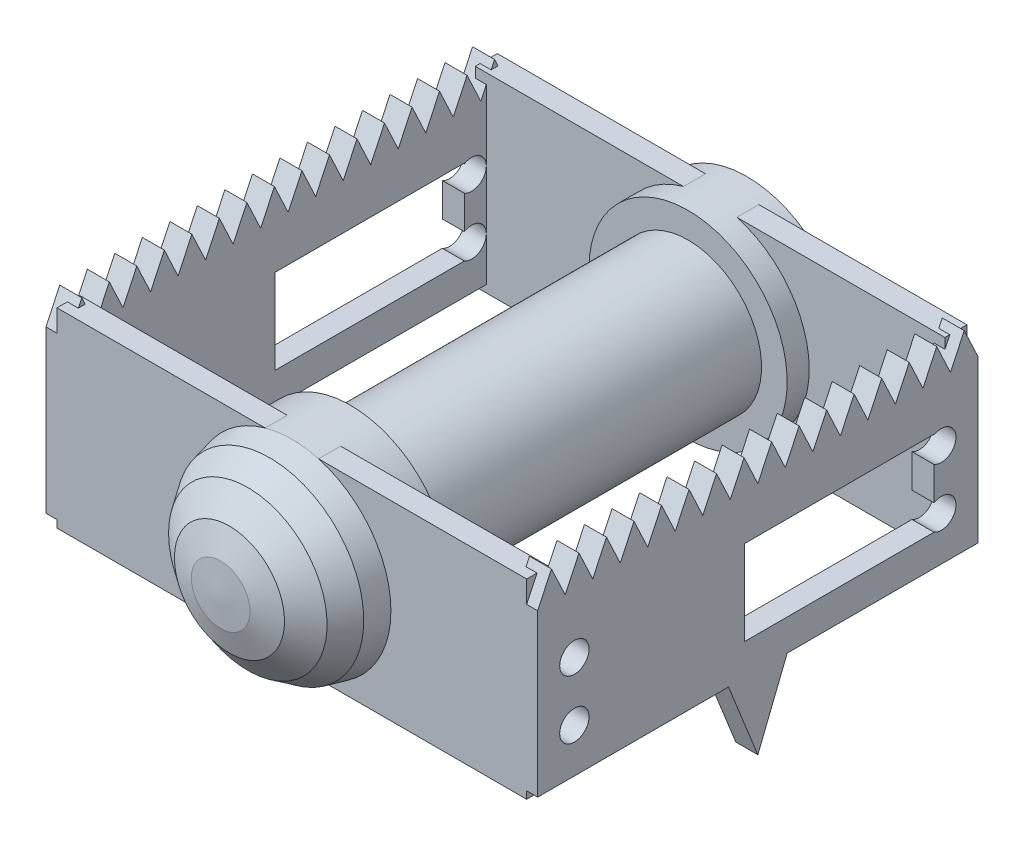
SolidWorks part; units mm, degrees
material "6061-T6 (SS)"
ref_plane "Alzado" through (0, 0, 0) normal (0, 0, 1) x (1, 0, 0)
ref_plane "Planta" through (0, 0, 0) normal (0, 1, 0) x (1, 0, 0)
ref_plane "Vista lateral" through (0, 0, 0) normal (1, 0, 0) x (0, 0, -1)
sketch "Sk_Eje_cuerpo" plane through (0, 0, 0) normal (0, 1, 0) x (1, 0, 0)
  line L0 (183.5, -84) -> (186, -84)
  line L1 (186, -84) -> (186, -92)
  line L2 (186, -92) -> (182.5, -92)
  line L3 (182.5, -92) -> (182.5, -138)
  line L4 (182.5, -138) -> (186, -138)
  line L5 (186, -138) -> (186, -146)
  line L6 (186, -146) -> (185.3, -149)
  line L7 (185.3, -149) -> (183.3, -152)
  line L8 (183.3, -152) -> (180, -154.5)
  line L9 (180, -154.5) -> (176.5, -155.7)
  line L10 (176.5, -155.7) -> (172.5, -156)
  line L11 (172.5, -156) -> (172.5, -147)
  line L12 (172.5, -147) -> (183.5, -147)
  line L13 (183.5, -147) -> (183.5, -138.5)
  line L14 (183.5, -138.5) -> (178.8, -138.5)
  line L15 (178.8, -138.5) -> (178.8, -91.5)
  line L16 (178.8, -91.5) -> (183.5, -91.5)
  line L17 (183.5, -91.5) -> (183.5, -84)
  line L18 (172.5, -62.1) -> (172.5, -160) construction
revolve "Eje_cuerpo" add sketch "Sk_Eje_cuerpo" angle 360 about L18
sketch "Sk_Placa_delantera" plane through (0, 0, 0) normal (1, 0, 0) x (0, 0, -1)
  line L0 (-86, -12) -> (-112, -12)
  line L1 (-112, -12) -> (-116, -22)
  line L2 (-116, -22) -> (-120, -12)
  line L3 (-120, -12) -> (-146, -12)
  line L4 (-146, -12) -> (-146, 10)
  line L5 (-146, 10) -> (-144.125, 14)
  line L6 (-144.125, 14) -> (-142.25, 10)
  line L7 (-142.25, 10) -> (-140.375, 14)
  line L8 (-140.375, 14) -> (-138.5, 10)
  line L9 (-138.5, 10) -> (-136.625, 14)
  line L10 (-136.625, 14) -> (-134.75, 10)
  line L11 (-134.75, 10) -> (-132.875, 14)
  line L12 (-132.875, 14) -> (-131, 10)
  line L13 (-131, 10) -> (-129.125, 14)
  line L14 (-129.125, 14) -> (-127.25, 10)
  line L15 (-127.25, 10) -> (-125.375, 14)
  line L16 (-125.375, 14) -> (-123.5, 10)
  line L17 (-123.5, 10) -> (-121.625, 14)
  line L18 (-121.625, 14) -> (-119.75, 10)
  line L19 (-119.75, 10) -> (-117.875, 14)
  line L20 (-117.875, 14) -> (-116, 10)
  line L21 (-116, 10) -> (-114.125, 14)
  line L22 (-114.125, 14) -> (-112.25, 10)
  line L23 (-112.25, 10) -> (-110.375, 14)
  line L24 (-110.375, 14) -> (-108.5, 10)
  line L25 (-108.5, 10) -> (-106.625, 14)
  line L26 (-106.625, 14) -> (-104.75, 10)
  line L27 (-104.75, 10) -> (-102.875, 14)
  line L28 (-102.875, 14) -> (-101, 10)
  line L29 (-101, 10) -> (-99.125, 14)
  line L30 (-99.125, 14) -> (-97.25, 10)
  line L31 (-97.25, 10) -> (-95.375, 14)
  line L32 (-95.375, 14) -> (-93.5, 10)
  line L33 (-93.5, 10) -> (-91.625, 14)
  line L34 (-91.625, 14) -> (-89.75, 10)
  line L35 (-89.75, 10) -> (-87.875, 14)
  line L36 (-87.875, 14) -> (-86, 10)
  line L37 (-86, 10) -> (-86, -12)
extrude "Placa_delantera" add sketch "Sk_Placa_delantera" along normal blind 3 from offset 203
sketch3d "Sk_Agujero_Placa_delantera_1"
  line L0 (201.5, -6, 91) -> (207.5, -6, 91)
  dimension "D1" = 6
sweep "Agujero_Placa_delantera_1" cut path "Sk_Agujero_Placa_delantera_1" circular profile diameter 4 parameters "D3"=4
sketch3d "Sk_Agujero_Placa_delantera_2"
  line L0 (201.5, 2, 91) -> (207.5, 2, 91)
  dimension "D1" = 6
sweep "Agujero_Placa_delantera_2" cut path "Sk_Agujero_Placa_delantera_2" circular profile diameter 4 parameters "D3"=4
sketch3d "Sk_Agujero_Placa_delantera_3"
  line L0 (201.5, -6, 141) -> (207.5, -6, 141)
  dimension "D1" = 6
sweep "Agujero_Placa_delantera_3" cut path "Sk_Agujero_Placa_delantera_3" circular profile diameter 4 parameters "D3"=4
sketch3d "Sk_Agujero_Placa_delantera_4"
  line L0 (201.5, 2, 141) -> (207.5, 2, 141)
  dimension "D1" = 6
sweep "Agujero_Placa_delantera_4" cut path "Sk_Agujero_Placa_delantera_4" circular profile diameter 4 parameters "D3"=4
sketch "Sk_Placa_trasera" plane through (0, 0, 0) normal (1, 0, 0) x (0, 0, -1)
  line L0 (-86, -12) -> (-146, -12)
  line L1 (-146, -12) -> (-146, 10)
  line L2 (-146, 10) -> (-144.125, 14)
  line L3 (-144.125, 14) -> (-142.25, 10)
  line L4 (-142.25, 10) -> (-140.375, 14)
  line L5 (-140.375, 14) -> (-138.5, 10)
  line L6 (-138.5, 10) -> (-136.625, 14)
  line L7 (-136.625, 14) -> (-134.75, 10)
  line L8 (-134.75, 10) -> (-132.875, 14)
  line L9 (-132.875, 14) -> (-131, 10)
  line L10 (-131, 10) -> (-129.125, 14)
  line L11 (-129.125, 14) -> (-127.25, 10)
  line L12 (-127.25, 10) -> (-125.375, 14)
  line L13 (-125.375, 14) -> (-123.5, 10)
  line L14 (-123.5, 10) -> (-121.625, 14)
  line L15 (-121.625, 14) -> (-119.75, 10)
  line L16 (-119.75, 10) -> (-117.875, 14)
  line L17 (-117.875, 14) -> (-116, 10)
  line L18 (-116, 10) -> (-114.125, 14)
  line L19 (-114.125, 14) -> (-112.25, 10)
  line L20 (-112.25, 10) -> (-110.375, 14)
  line L21 (-110.375, 14) -> (-108.5, 10)
  line L22 (-108.5, 10) -> (-106.625, 14)
  line L23 (-106.625, 14) -> (-104.75, 10)
  line L24 (-104.75, 10) -> (-102.875, 14)
  line L25 (-102.875, 14) -> (-101, 10)
  line L26 (-101, 10) -> (-99.125, 14)
  line L27 (-99.125, 14) -> (-97.25, 10)
  line L28 (-97.25, 10) -> (-95.375, 14)
  line L29 (-95.375, 14) -> (-93.5, 10)
  line L30 (-93.5, 10) -> (-91.625, 14)
  line L31 (-91.625, 14) -> (-89.75, 10)
  line L32 (-89.75, 10) -> (-87.875, 14)
  line L33 (-87.875, 14) -> (-86, 10)
  line L34 (-86, 10) -> (-86, -12)
extrude "Placa_trasera" add sketch "Sk_Placa_trasera" along normal blind 3 from offset 139
sketch3d "Sk_Agujero_Placa_trasera_1"
  line L0 (137.5, -6, 91) -> (143.5, -6, 91)
  dimension "D1" = 6
sweep "Agujero_Placa_trasera_1" cut path "Sk_Agujero_Placa_trasera_1" circular profile diameter 4 parameters "D3"=4
sketch3d "Sk_Agujero_Placa_trasera_2"
  line L0 (137.5, 2, 91) -> (143.5, 2, 91)
  dimension "D1" = 6
sweep "Agujero_Placa_trasera_2" cut path "Sk_Agujero_Placa_trasera_2" circular profile diameter 4 parameters "D3"=4
sketch3d "Sk_Agujero_Placa_trasera_3"
  line L0 (137.5, -6, 141) -> (143.5, -6, 141)
  dimension "D1" = 6
sweep "Agujero_Placa_trasera_3" cut path "Sk_Agujero_Placa_trasera_3" circular profile diameter 4 parameters "D3"=4
sketch3d "Sk_Agujero_Placa_trasera_4"
  line L0 (137.5, 2, 141) -> (143.5, 2, 141)
  dimension "D1" = 6
sweep "Agujero_Placa_trasera_4" cut path "Sk_Agujero_Placa_trasera_4" circular profile diameter 4 parameters "D3"=4
sketch "Sk_Marco_interior" plane through (0, 0, 0) normal (0, 0, 1) x (1, 0, 0)
  line L0 (140.5, -13) -> (204.5, -13)
  line L1 (204.5, -13) -> (204.5, 13)
  line L2 (204.5, 13) -> (140.5, 13)
  line L3 (140.5, 13) -> (140.5, -13)
  circle A0 centre (172.5, 0) radius 11
  dimension "DIAM1" = 22
extrude "Marco_interior" add sketch "Sk_Marco_interior" along normal blind 3 from offset 86
sketch "Sk_Marco_exterior" plane through (0, 0, 0) normal (0, 0, 1) x (1, 0, 0)
  line L0 (140.5, -13) -> (204.5, -13)
  line L1 (204.5, -13) -> (204.5, 13)
  line L2 (204.5, 13) -> (140.5, 13)
  line L3 (140.5, 13) -> (140.5, -13)
  circle A0 centre (172.5, 0) radius 11
  dimension "DIAM2" = 22
extrude "Marco_exterior" add sketch "Sk_Marco_exterior" along normal blind 3 from offset 143
ref_axis "Eje_pedal" through (172.5, 0, 146) along (0, 0, -1)
sketch "Croquis17" plane through (206, 0, 0) normal (1, 0, 0) x (0, 0, -1)
  line L0 (-92, 3.8293) -> (-117.7956, 3.8293)
  line L1 (-92, 10) -> (-92, -10) construction
  line L2 (-92, 13.5) -> (-92, -13.5) construction
  line L3 (-117.7956, 3.8293) -> (-117.7956, -7.7321)
  line L4 (-117.7956, -7.7321) -> (-92, -7.7321)
  line L5 (-92, -7.7321) -> (-92, 3.8293)
  circle A0 centre (-91, -6) radius 2 construction
extrude "Cortar-Extruir1" cut sketch "Croquis17" against normal blind 10
ref_plane "Plano1" through (172, 0, 0) normal (1, 0, 0) x (0, 0, -1)
mirror "Simetría1" about plane through (172, 0, 0) normal (1, 0, 0) of "Cortar-Extruir1"
